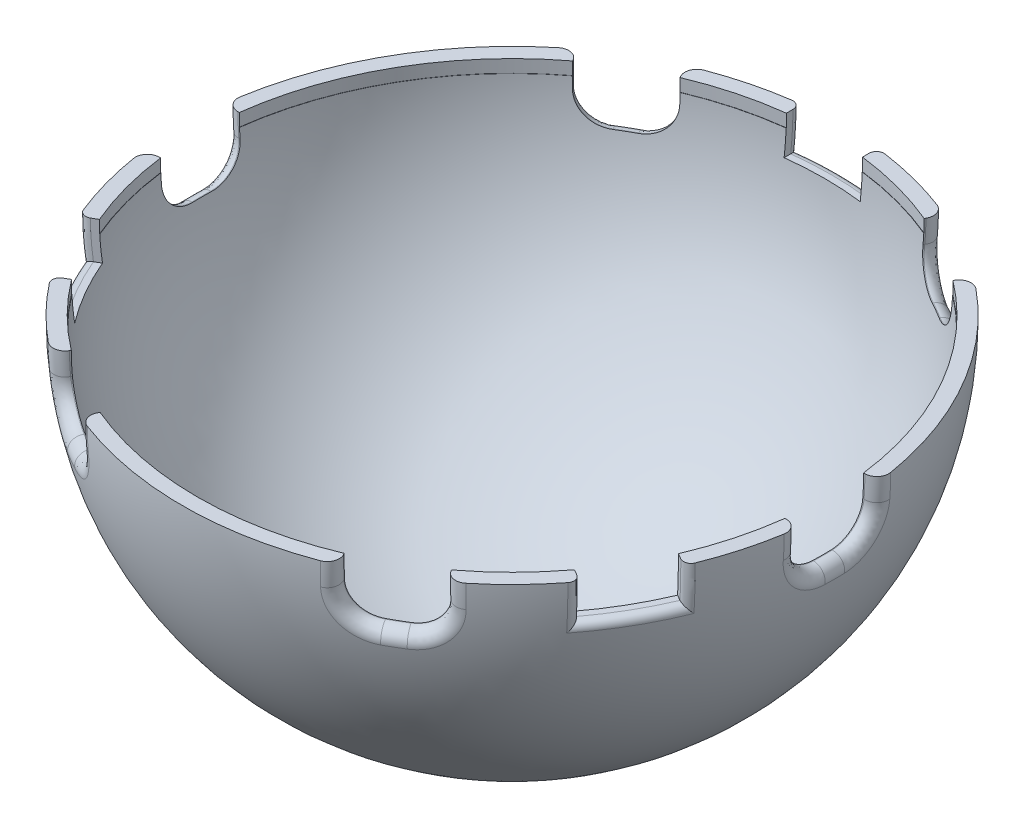
SolidWorks part; units mm, degrees
ref_plane "Front Plane" through (0, 0, 0) normal (0, 0, 1) x (1, 0, 0)
ref_plane "Top Plane" through (0, 0, 0) normal (0, 1, 0) x (1, 0, 0)
ref_plane "Right Plane" through (0, 0, 0) normal (1, 0, 0) x (0, 0, -1)
ref_axis "Axis1" through (-88.99, 0, 0) along (1, 0, 0)
ref_axis "Axis2" through (0, 0, 55) along (0, 0, -1)
ref_axis "Axis3" through (0, 18.7938, 0) along (0, -1, 0)
sketch "Sketch3" plane through (0, 0, 0) normal (0, 0, 1) x (1, 0, 0)
  line L0 (-88.99, 0) -> (88.99, 0) construction
  line L1 (-22, 0) -> (0, 0)
  line L2 (0, 0) -> (0, -22)
  arc A0 (-22, 0) -> (0, -22) centre (0, 0) ccw
revolve "Revolve1" add sketch "Sketch3" angle 360 about axis through (0, 18.7938, 0) along (0, -1, 0)
sketch "Sketch4" plane through (0, 0, 0) normal (0, 0, 1) x (1, 0, 0)
  line L0 (21, 0) -> (0, 0)
  line L1 (0, 0) -> (0, -21)
  arc A0 (21, 0) -> (0, -21) centre (0, 0) cw
revolve "Cut-Revolve1" cut sketch "Sketch4" angle 360 about axis through (0, 18.7938, 0) along (0, -1, 0)
sketch "Sketch5" plane through (0, 0, 0) normal (0, 1, 0) x (1, 0, 0)
  circle A0 centre (0, 0) radius 21
extrude "Cut-Extrude1" cut sketch "Sketch5" against normal blind 0.85
sketch "Sketch33" plane through (0, 0, 0) normal (0, 1, 0) x (1, 0, 0)
  line L1 (-2.54, 19.0556) -> (2.54, 19.0556)
  line L2 (-2.54, 19.0556) -> (-2.54, 22.9444)
  line L3 (-2.54, 22.9444) -> (2.54, 22.9444)
  line L4 (2.54, 19.0556) -> (2.54, 22.9444)
  line L5 (-2.54, 19.0556) -> (2.54, 22.9444) construction
  line L6 (-2.54, 22.9444) -> (2.54, 19.0556) construction
  circle A0 centre (0, 0) radius 21 construction
  point P0 (0, 21)
extrude "Cut-Extrude11" cut sketch "Sketch33" against normal blind 2.5
fillet "Fillet4" radius 0.5 3 edges at (-2.54, -1.2521, -21.817) (2.54, -1.2521, -21.817) (0, -2.5, -21.8575)
pattern_circular "CirPattern3" count 3 every 120 about axis through (0, 18.7938, 0) along (0, -1, 0) of "Cut-Extrude11", "Fillet4"
sketch "Sketch42" plane through (0, 0, 0) normal (0, 1, 0) x (1, 0, 0)
  line L1 (17.1558, 2.625) -> (24.769, 2.625)
  line L2 (17.1558, 2.625) -> (17.1558, -2.625)
  line L3 (17.1558, -2.625) -> (24.769, -2.625)
  line L4 (24.769, 2.625) -> (24.769, -2.625)
  line L5 (17.1558, 2.625) -> (24.769, -2.625) construction
  line L6 (17.1558, -2.625) -> (24.769, 2.625) construction
  point P0 (20.9624, 0)
extrude "Cut-Extrude12" cut sketch "Sketch42" against normal blind 3.5
fillet "Fillet5" radius 2 2 edges at (21.0499, -3.5, 2.625) (21.0499, -3.5, -2.625)
fillet "Fillet6" radius 0.8 5 edges at (21.8299, -0.7504, 2.625) (21.7051, -3.0639, 1.8717) (21.7198, -3.5, 0) (21.7177, -2.7504, -2.1859) (21.8299, -0.7504, -2.625)
pattern_circular "CirPattern8" count 6 over 360 about axis through (0, 18.7938, 0) along (0, -1, 0) of "Cut-Extrude12", "Fillet5", "Fillet6"
